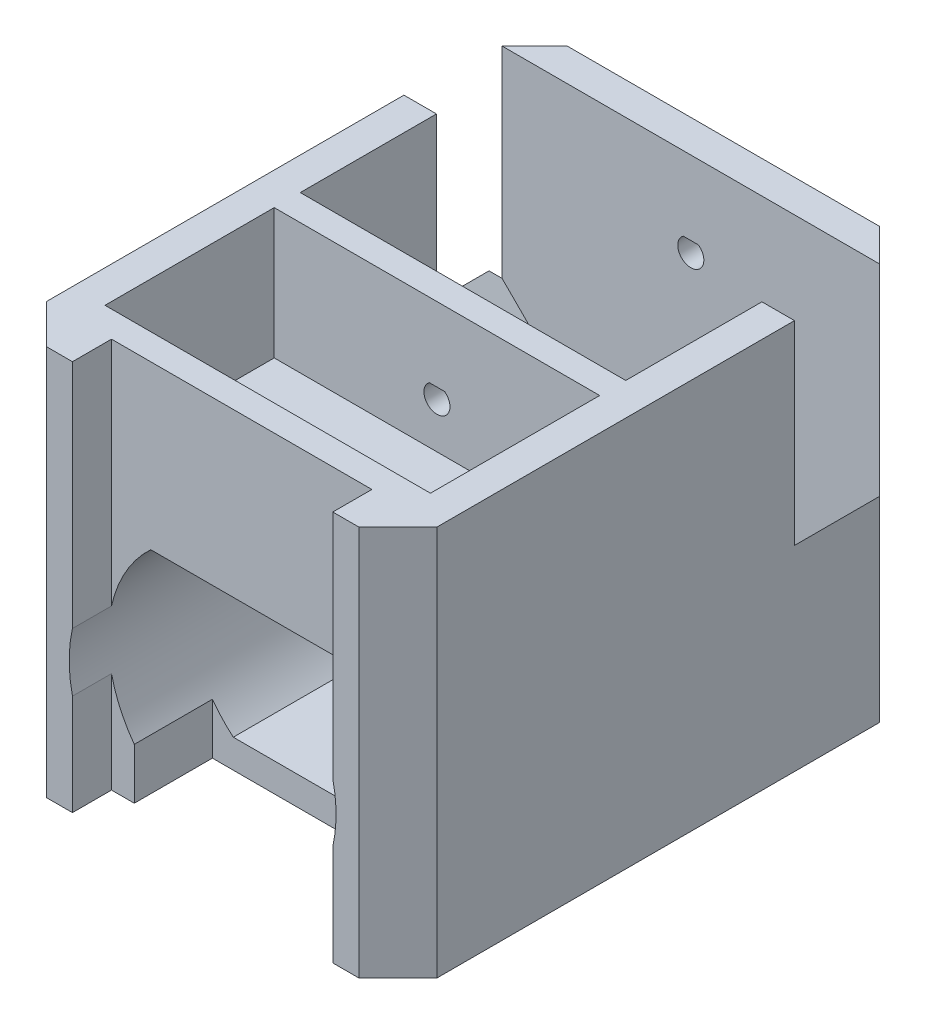
SolidWorks part; units mm, degrees
ref_plane "Front Plane" through (0, 0, 0) normal (0, 0, 1) x (1, 0, 0)
ref_plane "Top Plane" through (0, 0, 0) normal (0, 1, 0) x (1, 0, 0)
ref_plane "Right Plane" through (0, 0, 0) normal (1, 0, 0) x (0, 0, -1)
sketch "Sketch1" plane through (0, 0, 0) normal (0, 0, 1) x (1, 0, 0)
  line L1 (-15, -20) -> (15, -20)
  line L2 (-15, -20) -> (-15, 20)
  line L3 (-15, 20) -> (15, 20)
  line L4 (15, -20) -> (15, 20)
  line L5 (-15, -20) -> (15, 20) construction
  line L6 (-15, 20) -> (15, -20) construction
  point P0 (0, 0)
  dimension "D1" = 30
  dimension "D2" = 40
extrude "Boss-Extrude1" add sketch "Sketch1" along normal blind 40
sketch "Sketch2" plane through (0, 0, 40) normal (0, 0, 1) x (1, 0, 0)
  line L5 (-6.9866, -2.5) -> (6.9866, -2.5)
  line L7 (-6.6464, -17.803) -> (6.6464, -17.803)
  arc A4 (-6.9866, -2.5) -> (-6.6464, -17.803) centre (0, -10) ccw
  arc A5 (6.6464, -17.803) -> (6.9866, -2.5) centre (0, -10) ccw
  point P0 (0, -10)
  dimension "D2" = 20.5
extrude "Cut-Extrude1" cut sketch "Sketch2" against normal blind 35
sketch "Sketch4" plane through (0, 20, 0) normal (0, 1, 0) x (1, 0, 0)
  line L1 (-12.5, -37.5) -> (12.5, -37.5)
  line L2 (-12.5, -37.5) -> (-12.5, -2.5)
  line L3 (-12.5, -2.5) -> (12.5, -2.5)
  line L4 (12.5, -37.5) -> (12.5, -2.5)
  point P0 (0, -20)
  dimension "D1" = 25
  dimension "D2" = 35
extrude "Cut-Extrude3" cut sketch "Sketch4" against normal blind 20
sketch "Sketch5" plane through (0, 0, 0) normal (0, 1, 0) x (1, 0, 0)
  line L0 (12.5, -37.5) -> (12.5, -2.5) construction
  line L1 (-12.5, -2.5) -> (12.5, -2.5)
  line L2 (-12.5, -2.5) -> (-12.5, -20)
  line L3 (-12.5, -20) -> (12.5, -20)
  line L4 (12.5, -2.5) -> (12.5, -20)
extrude "Cut-Extrude4" cut sketch "Sketch5" against normal blind 20
sketch "Sketch13" plane through (0, 0, 0) normal (0, 1, 0) x (1, 0, 0)
  line L0 (12.5, -37.5) -> (12.5, -20) construction
  line L1 (-12.5, -20) -> (12.5, -20)
  line L2 (-12.5, -20) -> (-12.5, -22.0007)
  line L3 (-12.5, -22.0007) -> (12.5, -22.0007)
  line L4 (12.5, -20) -> (12.5, -22.0007)
extrude "Boss-Extrude3" add sketch "Sketch13" along normal up to surface (20 mm away) up to face at (0, 20, 20)
sketch "Sketch8" plane through (0, 0, 40) normal (0, 0, 1) x (1, 0, 0)
  line L0 (-0.5467, -9.1627) -> (0.5467, -9.1627)
  arc A3 (-0.5467, -9.1627) -> (0.5467, -9.1627) centre (0, -10.2278) ccw
extrude "Cut-Extrude5" cut sketch "Sketch8" against normal up to surface (40 mm away) up to face at (0, 0, 0)
sketch "Sketch9" plane through (0, 0, 0) normal (0, 0, -1) x (-1, 0, 0)
  line L1 (-0.5842, 4.3116) -> (0.5842, 4.3116)
  arc A0 (-0.5842, 4.3116) -> (0.5842, 4.3116) centre (0, 3.5) ccw
  dimension "D2" = 2
extrude "Cut-Extrude6" cut sketch "Sketch9" against normal up to surface (40 mm away) up to face at (0, -10.1897, 40)
sketch "Sketch10" plane through (0, 0, 40) normal (0, 0, 1) x (1, 0, 0)
  line L0 (15, -20) -> (15, 20) construction
  line L1 (-15, 20) -> (15, 20)
  line L2 (-15, 20) -> (-15, 10)
  line L3 (-15, 10) -> (15, 10)
  line L4 (15, 20) -> (15, 10)
  dimension "D1" = 10
extrude "Cut-Extrude9" cut sketch "Sketch10" against normal up to surface (40 mm away) up to face at (0, 3.4058, 0)
chamfer "Chamfer2" distance 3 angle 45 4 edges at (15, -5, 0) (15, -5, 40) (-15, -5, 40) (-15, -5, 0)
sketch "Sketch16" plane through (-12.5, 0, 0) normal (1, 0, 0) x (0, 0, -1)
  line L1 (-2.5, 10) -> (-9.5368, 10)
  line L2 (-2.5, 10) -> (-2.5, -4.4568)
  line L4 (-9.5368, 10) -> (-9.5368, -4.4568)
  line L5 (-9.5368, -4.4568) -> (-2.5, -4.4568)
extrude "Cut-Extrude10" cut sketch "Sketch16" against normal mid plane 57
chamfer "Chamfer3" distance 3 angle 45 2 edges at (12.5, -4.4568, 6.0184) (-12.5, -4.4568, 6.0184)
sketch "Sketch17" plane through (0, 10, 0) normal (0, 1, 0) x (1, 0, 0)
  line L0 (12.5, -37.5) -> (12.5, -22.0007) construction
  line L1 (-12.5, -37.5) -> (12.5, -37.5)
  line L2 (-12.5, -37.5) -> (-12.5, -35)
  line L3 (-12.5, -35) -> (12.5, -35)
  line L4 (12.5, -37.5) -> (12.5, -35)
  dimension "D1" = 2.5
extrude "Boss-Extrude4" add sketch "Sketch17" against normal up to surface (10 mm away) up to face at (0, 0, 29.7504)
sketch "Sketch18" plane through (0, 10, 0) normal (0, 1, 0) x (1, 0, 0)
  line L0 (-10, -40) -> (10, -40)
  line L1 (-12, -40) -> (12, -40) construction
  line L5 (-10, -40) -> (10, -40)
  line L6 (-10, -40) -> (-10, -37)
  line L7 (-10, -37) -> (10, -37)
  line L8 (10, -40) -> (10, -37)
  point P5 (0, -40)
  line M15 (-12, -40) -> (12, -40)
  dimension "D1" = 20
  dimension "D2" = 3
extrude "Cut-Extrude13" cut sketch "Sketch18" against normal up to surface (30 mm away) contours L8 L7 L6 M15 region at (0, 10, 38.5) up to face at (0, -20, 11.25)
sketch "Sketch19" plane through (0, -20, 0) normal (0, -1, 0) x (1, 0, 0)
  line L0 (-8.25, 37) -> (8.25, 37)
  line L1 (10, 37) -> (-10, 37) construction
  line L5 (-8.25, 37) -> (8.25, 37)
  line L6 (-8.25, 37) -> (-8.25, 31)
  line L7 (-8.25, 31) -> (8.25, 31)
  line L8 (8.25, 37) -> (8.25, 31)
  point P5 (0, 37)
  line M18 (10, 37) -> (-10, 37)
  dimension "D1" = 16.5
  dimension "D2" = 6
extrude "Cut-Extrude14" cut sketch "Sketch19" against normal blind 10 contours L8 L6 L7 M18 region at (0, -20, 34)
sketch "Sketch20" plane through (0, 0, 20) normal (0, 0, -1) x (-1, 0, 0)
  line L0 (10.25, -10) -> (12.5, -10)
  line L1 (-12.5, -10) -> (-10.25, -10)
  line L2 (-12.5, -10) -> (-12.5, -20)
  line L3 (-12.5, -20) -> (12.5, -20)
  line L4 (12.5, -20) -> (12.5, 10)
  line L5 (12.5, 10) -> (-12.5, 10)
  line L6 (-12.5, 10) -> (-12.5, -20)
  line L7 (-12.5, -20) -> (12.5, -20)
  line L8 (12.5, -20) -> (12.5, -10)
  line L10 (-12.5, -10) -> (-12.5, -20)
  line L11 (-12.5, -20) -> (12.5, -20)
  line L12 (12.5, -10) -> (12.5, -20)
  line L13 (-6.6464, -17.803) -> (6.6464, -17.803)
  arc A0 (6.6464, -17.803) -> (6.9866, -2.5) centre (0, -10) ccw construction
  arc A1 (6.6464, -17.803) -> (10.25, -10) centre (0, -10) ccw
  arc A2 (-6.9866, -2.5) -> (-6.6464, -17.803) centre (0, -10) ccw construction
  arc A3 (-10.25, -10) -> (-6.6464, -17.803) centre (0, -10) ccw
  line M7 (12.5, -20) -> (12.5, 10)
  line M9 (-12.5, 10) -> (-12.5, -20)
  line M10 (-12.5, -20) -> (12.5, -20)
  line M11 (6.6464, -17.803) -> (-6.6464, -17.803)
  arc M12 (-6.6464, -17.803) -> (-6.9866, -2.5) centre (0, -10) cw
  arc M14 (6.9866, -2.5) -> (6.6464, -17.803) centre (0, -10) cw
  dimension "D1" = 0
extrude "Boss-Extrude5" add sketch "Sketch20" along normal blind 8.5 contours L1 L0 M9 M10 M7 M14 M11 M12 region at (-11.375, -10.2693, 20)
sketch "Sketch22" plane through (0, 0, 11.5) normal (0, 0, -1) x (-1, 0, 0)
  line L0 (12.5, -20) -> (12.5, -10) construction
  line L1 (-12.5, -20) -> (12.5, -20)
  line L2 (-12.5, -20) -> (-12.5, -15)
  line L3 (-12.5, -15) -> (12.5, -15)
  line L4 (12.5, -20) -> (12.5, -15)
extrude "Boss-Extrude6" add sketch "Sketch22" along normal blind 1
